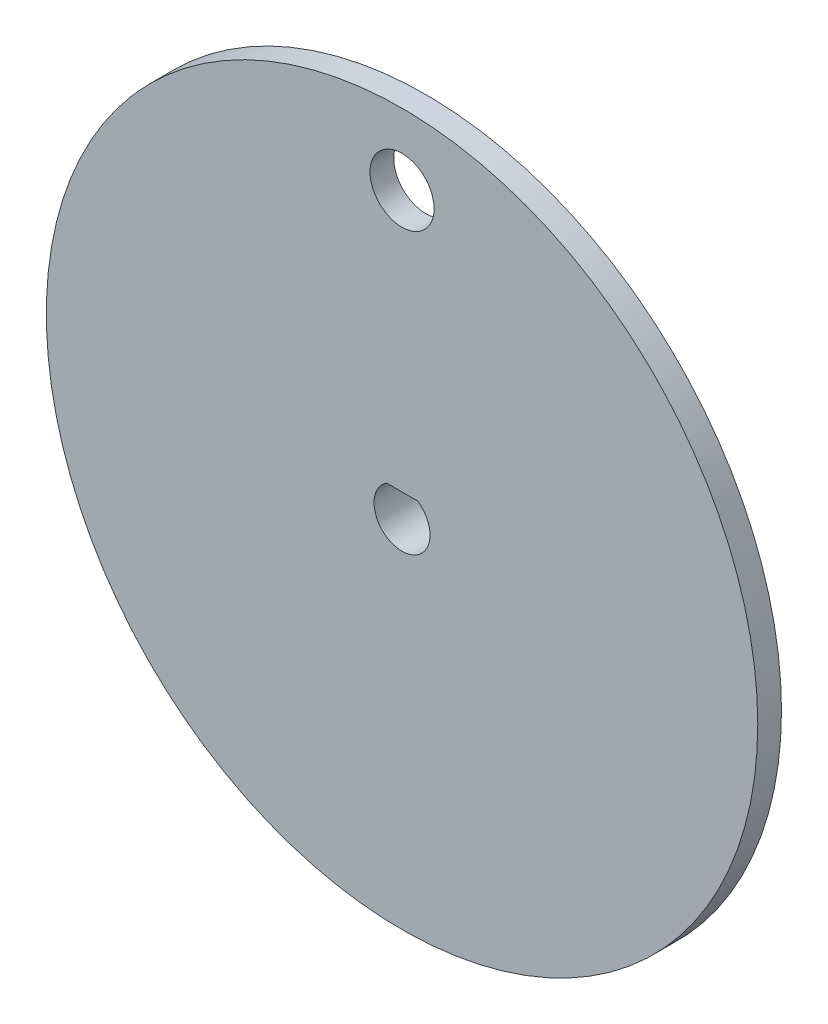
SolidWorks part; units mm, degrees
ref_plane "Front Plane" through (0, 0, 0) normal (0, 0, 1) x (1, 0, 0)
ref_plane "Top Plane" through (0, 0, 0) normal (0, 1, 0) x (1, 0, 0)
ref_plane "Right Plane" through (0, 0, 0) normal (1, 0, 0) x (0, 0, -1)
sketch "Sketch1" plane through (0, 0, 0) normal (0, 0, 1) x (1, 0, 0)
  circle A0 centre (0, 0) radius 38.1
  dimension "D1" = 76.2
extrude "Boss-Extrude1" add sketch "Sketch1" along normal blind 2.54
sketch "Sketch2" plane through (0, 0, 2.54) normal (0, 0, 1) x (1, 0, 0)
  line L0 (0, 38.1) -> (0, -38.1) construction
  circle A0 centre (0, 0) radius 38.1 construction
  circle A2 centre (0, 30.48) radius 3.429
  dimension "D1" = 6.858
  dimension "D2" = 30.48
sketch "Sketch3" plane through (0, 0, 0) normal (0, 0, -1) x (-1, 0, 0)
  circle A0 centre (0, 0) radius 6.35
  dimension "D1" = 12.7
extrude "Boss-Extrude3" add sketch "Sketch3" along normal blind 19.05
extrude "Cut-Extrude1" cut sketch "Sketch2" against normal through all contours A2
sketch "Sketch4" plane through (0, 0, -19.05) normal (0, 0, -1) x (-1, 0, 0)
  line L0 (-1.6583, 2.5) -> (1.6583, 2.5)
  arc A0 (-1.6583, 2.5) -> (1.6583, 2.5) centre (0, 0) ccw
  point P1 (0, -3)
  dimension "D1" = 6
  dimension "D2" = 5.5
extrude "Cut-Extrude2" cut sketch "Sketch4" against normal through all
